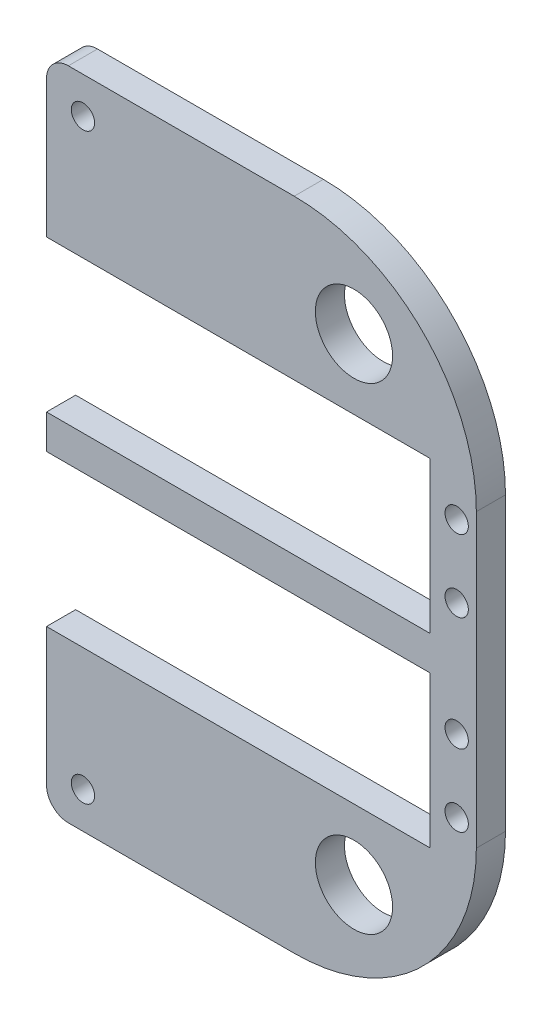
SolidWorks part; units mm, degrees
ref_plane "正面" through (0, 0, 0) normal (0, 0, 1) x (1, 0, 0)
ref_plane "平面" through (0, 0, 0) normal (0, 1, 0) x (1, 0, 0)
ref_plane "右側面" through (0, 0, 0) normal (1, 0, 0) x (0, 0, -1)
sketch "ｽｹｯﾁ1" plane through (0, 0, 0) normal (0, 0, 1) x (1, 0, 0)
  line L0 (-32, -29.25) -> (-32, 54.75) construction
  line L1 (-32, -32.25) -> (27, -32.25)
  line L2 (-32, -32.25) -> (-32, 57.75)
  line L3 (-32, 57.75) -> (27, 57.75)
  line L4 (27, -32.25) -> (27, 57.75)
  line L5 (2, -32.25) -> (-29, -32.25) construction
  line L6 (-29, 57.75) -> (2, 57.75) construction
  line L7 (27, 57.75) -> (27, -32.25) construction
  line L9 (-20, 10.25) -> (20, 10.25) construction
  line L10 (-32, -10.4) -> (20.65, -10.4)
  line L11 (-32, -10.4) -> (-32, 10.4)
  line L12 (-32, 10.4) -> (20.65, 10.4)
  line L13 (20.65, -10.4) -> (20.65, 10.4)
  line L14 (-32, 15.1) -> (20.65, 15.1)
  line L15 (-32, 15.1) -> (-32, 35.9)
  line L16 (-32, 35.9) -> (20.65, 35.9)
  line L17 (20.65, 15.1) -> (20.65, 35.9)
  line L18 (20, -10.25) -> (-20, -10.25) construction
  line L19 (20.5, 9.25) -> (20.5, -9.25) construction
  line L20 (-20, 35.75) -> (20, 35.75) construction
  line L21 (20, 15.25) -> (-20, 15.25) construction
  line L22 (20.5, 34.75) -> (20.5, 16.25) construction
  circle A4 centre (24.3, 30.45) radius 1.6
  circle A5 centre (24.3, 20.55) radius 1.6
  circle A6 centre (24.3, 4.95) radius 1.6
  circle A7 centre (24.3, -4.95) radius 1.6
  circle A8 centre (10.2, -20) radius 5.3
  circle A9 centre (10.2, 45.5) radius 5.3
  circle A10 centre (10.2, -20) radius 5.3 construction
  dimension "D5" = 0.15
  dimension "D6" = 3.2
  dimension "D1" = 0
  dimension "D2" = 0
  dimension "D3" = 0
  dimension "D4" = 0
  dimension "D7" = 0.15
  dimension "D8" = 0.15
  dimension "D9" = 0.15
  dimension "D10" = 0.15
  dimension "D11" = 0.15
extrude "ﾎﾞｽ - 押し出し1" add sketch "ｽｹｯﾁ1" along normal blind 4 contours L17 L14 L2 L12 L13 L10 L1 L4 L3 L16 A9 A8 A7 A6 A5 A4 region at (-1.1773, 12.75, 0)
fillet "ﾌｨﾚｯﾄ1" radius 3 2 edges at (-32, 57.75, 2) (-32, -32.25, 2)
fillet "ﾌｨﾚｯﾄ2" radius 25 2 edges at (27, 57.75, 2) (27, -32.25, 2)
sketch "ｽｹｯﾁ2" plane through (0, 0, 0) normal (0, 0, -1) x (-1, 0, 0)
  circle A0 centre (27, 52.75) radius 1.6
  circle A1 centre (27, -27.25) radius 1.6
  dimension "D1" = 3.2
extrude "ｶｯﾄ - 押し出し1" cut sketch "ｽｹｯﾁ2" against normal blind 10
